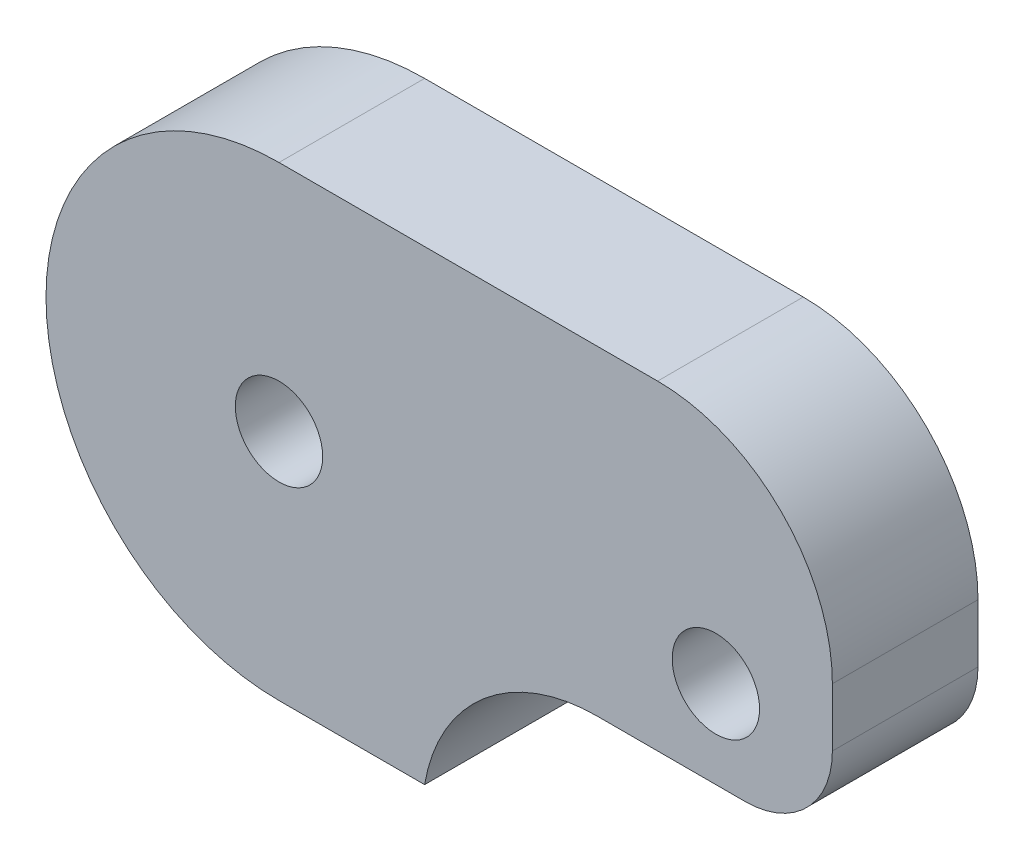
SolidWorks part; units mm, degrees
ref_plane "Plan de face" through (0, 0, 0) normal (0, 0, 1) x (1, 0, 0)
ref_plane "Plan de dessus" through (0, 0, 0) normal (0, 1, 0) x (1, 0, 0)
ref_plane "Plan de droite" through (0, 0, 0) normal (1, 0, 0) x (0, 0, -1)
sketch "Esquisse1" plane through (0, 0, 0) normal (0, 0, 1) x (1, 0, 0)
  line L0 (0, 0) -> (80, 0) construction
  line L1 (20, 0) -> (20, 23.8674) construction
  line L2 (0, 0) -> (0, 35) construction
  line L3 (0, 35) -> (55, 35) construction
  line L4 (0, 8) -> (34, 8) construction
  line L5 (82.6316, 13.5175) -> (85, 11.6762) construction
  line L6 (34, 8) -> (32.7289, 8) construction
  line L7 (0, -8) -> (55, -8) construction
  line L8 (55, 35) -> (55, -8) construction
  line L9 (0, -8) -> (20, -8) construction
  line L10 (20, -3) -> (34, -3)
  line L11 (20, -8) -> (20, -3)
  line L12 (34, -3) -> (34, 8)
  line L13 (15, 8) -> (34, 8)
  line L14 (15, -8) -> (20, -8)
  circle A0 centre (0, 0) radius 1.5 construction
  arc A1 (0, 8) -> (0, -8) centre (0, 0) ccw construction
  circle A2 centre (55, 35) radius 35 construction
  arc A3 (32.7289, 8) -> (82.6316, 13.5175) centre (55, 35) ccw construction
  arc A4 (82.6316, 13.5175) -> (87.5479, 10.0925) centre (85, 11.6762) cw construction
  arc A5 (55, -8) -> (87.5479, 10.0925) centre (55, 30.3227) ccw construction
  circle A6 centre (15, 0) radius 1.5
  arc A7 (15, 8) -> (15, -8) centre (15, 0) ccw
  circle A9 centre (30, 0) radius 1.5
  dimension "D3" = 3
  dimension "D4" = 35
  dimension "D6" = 70
  dimension "D7" = 3
  dimension "D8" = 8
  dimension "D9" = 30
  dimension "D10" = 15
  dimension "D11" = 15
  dimension "D1" = 20
  dimension "D2" = 80
  dimension "D5" = 55
  dimension "D12" = 3
  dimension "D13" = 4
extrude "Boss.-Extru.1" add sketch "Esquisse1" along normal blind 5
fillet "Congé1" radius 6 2 edges at (20, -3, 2.5) (34, 8, 2.5)
fillet "Congé2" radius 3 1 edges at (34, -3, 2.5)
